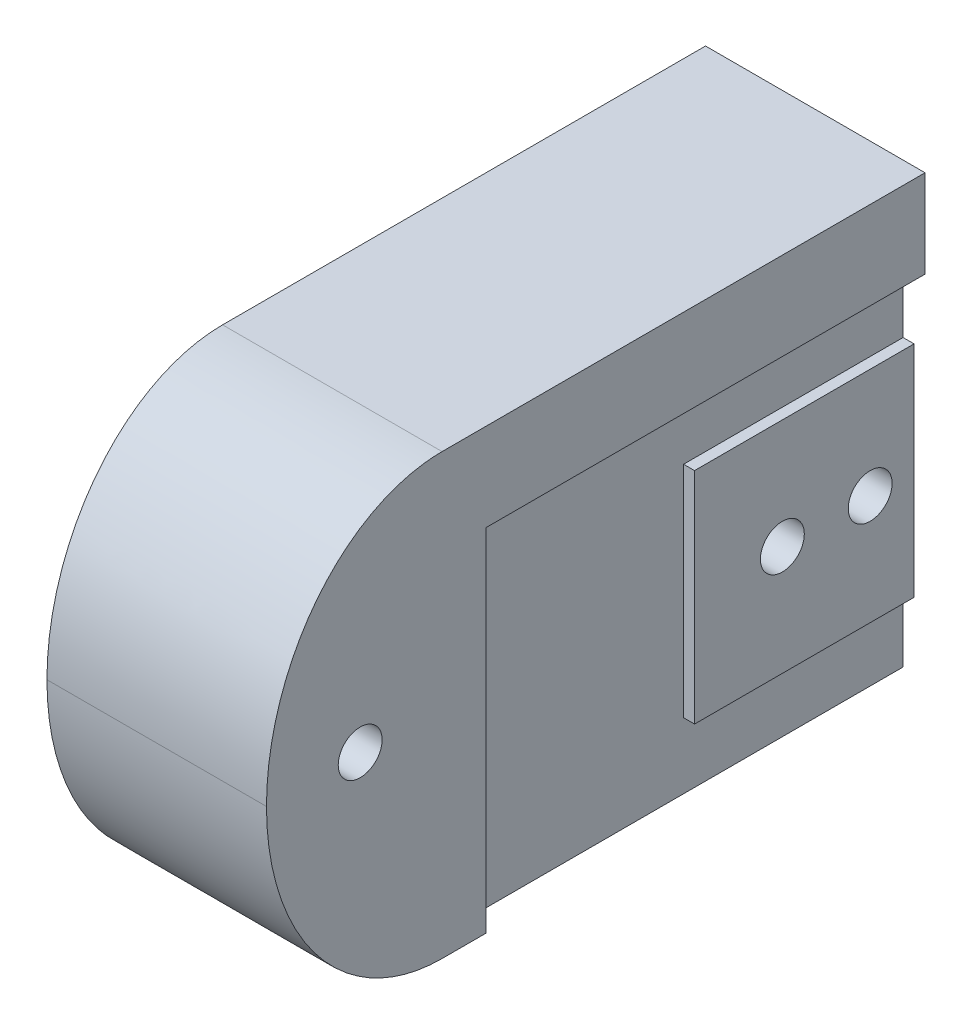
SolidWorks part; units mm, degrees
ref_plane "Ebene vorne" through (0, 0, 0) normal (0, 0, 1) x (1, 0, 0)
ref_plane "Ebene oben" through (0, 0, 0) normal (0, 1, 0) x (1, 0, 0)
ref_plane "Ebene rechts" through (0, 0, 0) normal (1, 0, 0) x (0, 0, -1)
sketch "Skizze1" plane through (0, 0, 0) normal (1, 0, 0) x (0, 0, -1)
  line L1 (-106.9542, 40.537) -> (43.0458, 40.537)
  line L2 (-106.9542, 40.537) -> (-106.9542, -59.463)
  line L3 (-106.9542, -59.463) -> (43.0458, -59.463)
  line L4 (43.0458, 40.537) -> (43.0458, -59.463)
  dimension "D1" = 150
  dimension "D2" = 100
extrude "Aufsatz-Linear austragen1" add sketch "Skizze1" along normal blind 50
sketch "Skizze2" plane through (50, 0, 0) normal (1, 0, 0) x (0, 0, -1)
  line L1 (43.0458, -59.463) -> (-56.9542, -59.463)
  line L2 (43.0458, -59.463) -> (43.0458, 20.537)
  line L3 (43.0458, 20.537) -> (-56.9542, 20.537)
  line L4 (-56.9542, -59.463) -> (-56.9542, 20.537)
  dimension "D1" = 100
  dimension "D2" = 80
extrude "Schnitt-Linear austragen1" cut sketch "Skizze2" against normal blind 5
sketch "Skizze3" plane through (45, 0, 0) normal (1, 0, 0) x (0, 0, -1)
  line L0 (43.0458, -59.463) -> (43.0458, 20.537) construction
  line L1 (-56.9542, -59.463) -> (43.0458, -59.463) construction
  line L2 (43.0458, 5.537) -> (-6.9542, 5.537)
  line L3 (43.0458, 5.537) -> (43.0458, -44.463)
  line L4 (43.0458, -44.463) -> (-6.9542, -44.463)
  line L5 (-6.9542, 5.537) -> (-6.9542, -44.463)
  dimension "D1" = 50
  dimension "D2" = 50
  dimension "D3" = 15
extrude "Aufsatz-Linear austragen2" add sketch "Skizze3" along normal blind 2.5
sketch "Skizze4" plane through (47.5, 0, 0) normal (1, 0, 0) x (0, 0, -1)
  line L0 (43.0458, -44.463) -> (43.0458, 5.537) construction
  circle A0 centre (33.0458, -19.463) radius 5
  circle A1 centre (13.0458, -19.463) radius 5
  dimension "D1" = 10
  dimension "D2" = 20
extrude "Schnitt-Linear austragen2" cut sketch "Skizze4" against normal blind 10
fillet "Verrundung1" radius 40 2 edges at (25, -59.463, 106.9542) (25, 40.537, 106.9542) second distance 50 first distance on face at (31.6667, -59.463, 40.2876) first distance on face at (25, 40.537, 31.9542)
sketch "Skizze5" plane through (0, 0, 0) normal (-1, 0, 0) x (0, 0, 1)
  circle A1 centre (85.6148, -9.463) radius 5
extrude "Schnitt-Linear austragen3" cut sketch "Skizze5" against normal blind 380
